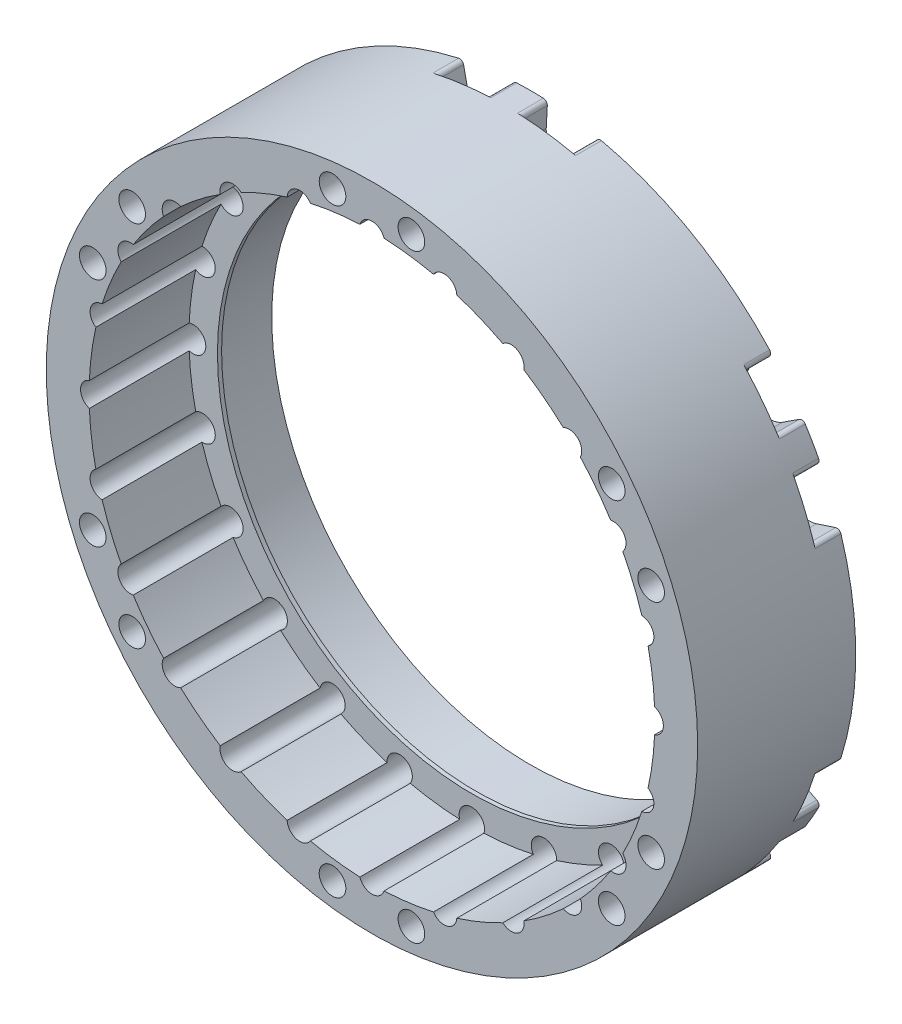
SolidWorks part; units mm, degrees
material "ABS"
ref_plane "Front Plane" through (0, 0, 0) normal (0, 0, 1) x (1, 0, 0)
ref_plane "Top Plane" through (0, 0, 0) normal (0, 1, 0) x (1, 0, 0)
ref_plane "Right Plane" through (0, 0, 0) normal (1, 0, 0) x (0, 0, -1)
sketch "CYC Master Sketch" plane through (0, 0, 0) normal (0, 0, 1) x (1, 0, 0)
  circle A0 centre (0, 0) radius 39.15
  circle A2 centre (0, 0) radius 33.5 construction
  circle A3 centre (-33.5, 0) radius 1.525
  circle A4 centre (-32.3585, 8.6704) radius 1.525
  circle A5 centre (-29.0119, 16.75) radius 1.525
  circle A6 centre (-23.6881, 23.6881) radius 1.525
  circle A7 centre (-16.75, 29.0119) radius 1.525
  circle A8 centre (-8.6704, 32.3585) radius 1.525
  circle A9 centre (0, 33.5) radius 1.525
  circle A10 centre (8.6704, 32.3585) radius 1.525
  circle A11 centre (16.75, 29.0119) radius 1.525
  circle A12 centre (23.6881, 23.6881) radius 1.525
  circle A13 centre (29.0119, 16.75) radius 1.525
  circle A14 centre (32.3585, 8.6704) radius 1.525
  circle A15 centre (33.5, 0) radius 1.525
  circle A16 centre (32.3585, -8.6704) radius 1.525
  circle A17 centre (29.0119, -16.75) radius 1.525
  circle A18 centre (23.6881, -23.6881) radius 1.525
  circle A19 centre (16.75, -29.0119) radius 1.525
  circle A20 centre (8.6704, -32.3585) radius 1.525
  circle A21 centre (0, -33.5) radius 1.525
  circle A22 centre (-8.6704, -32.3585) radius 1.525
  circle A23 centre (0, 0) radius 34
  circle A24 centre (-16.75, -29.0119) radius 1.525
  circle A25 centre (-23.6881, -23.6881) radius 1.525
  circle A26 centre (-29.0119, -16.75) radius 1.525
  circle A27 centre (-32.3585, -8.6704) radius 1.525
  circle A28 centre (0, 0) radius 31.05 construction
  circle A29 centre (0, 0) radius 24.975 construction
  circle A30 centre (0, 0) radius 36.325 construction
  circle A31 centre (4.7414, -36.0142) radius 1.6
  circle A32 centre (-4.7414, -36.0142) radius 1.6
  circle A33 centre (-28.8186, -22.1133) radius 1.6
  circle A34 centre (-33.5599, -13.901) radius 1.6
  circle A35 centre (-33.5599, 13.901) radius 1.6
  circle A36 centre (-28.8186, 22.1133) radius 1.6
  circle A37 centre (-4.7414, 36.0142) radius 1.6
  circle A38 centre (4.7414, 36.0142) radius 1.6
  circle A39 centre (28.8186, 22.1133) radius 1.6
  circle A40 centre (33.5599, 13.901) radius 1.6
  circle A41 centre (33.5599, -13.901) radius 1.6
  circle A42 centre (28.8186, -22.1133) radius 1.6
  point P47 (0, 0)
  point P72 (0, 0)
extrude "Gearbox Wall" add sketch "CYC Master Sketch" along normal blind 19 contours A0 A23 A13 A14 A15 A16 A17 A18 A19 A20 A21 A22 A3 A4 A5 A6 A7 A8 A9 A10 A11 A12 region at (-38.0427, 0, 0)
extrude "Gearbox Bottom" add sketch "CYC Master Sketch<3>" along normal blind 7 contours A21 A23 | A23 A20 | A20 A23 | A23 A19 | A19 A23 | A23 A18 | A18 A23 | A23 A17 | A17 A23 | A23 A16 | A16 A23 | A23 A15 | A15 A23 | A23 A14 | A14 A23 | A23 A13 | A13 A23 | A23 A12 | A12 A23 | A23 A11 | A11 A23 | A23 A10 | A10 A23 | A23 A9 | A9 A23 | A23 A8 | A8 A23 | A23 A7 | A7 A23 | A23 A6 | A6 A23 | A23 A5 | A5 A23 | A23 A4 | A4 A23 | A23 A3 | A3 A23 | A23 A22 | A22 A23 | A13 A23 A12 A11 A10 A9 A8 A7 A6 A5 A4 A3 A22 A21 A20 A19 A18 A17 A16 A15 A14 | A24 | A25 | A26 | A27 | A21 region at (-33.1078, 0, 0) region at (0, 0, 0) region at (-34.4188, 0, 0) region at (-31.9797, 8.5689, 0) region at (-33.246, 8.9082, 0) region at (-28.6722, 16.5539, 0) region at (-29.8076, 17.2094, 0) region at (-23.4108, 23.4108, 0) region at (-24.3378, 24.3378, 0) region at (-16.5539, 28.6722, 0) region at (-17.2094, 29.8076, 0) region at (-8.5689, 31.9797, 0) region at (-8.9082, 33.246, 0) region at (-8.9082, -33.246, 0) region at (-8.5689, -31.9797, 0) region at (0, 33.1078, 0) region at (0, 34.4188, 0) region at (0, -33.1078, 0) region at (8.5689, 31.9797, 0) region at (8.9082, 33.246, 0) region at (8.9082, -33.246, 0) region at (8.5689, -31.9797, 0) region at (16.5539, 28.6722, 0) region at (17.2094, 29.8076, 0) region at (17.2094, -29.8076, 0) region at (16.5539, -28.6722, 0) region at (23.4108, 23.4108, 0) region at (24.3378, 24.3378, 0) region at (24.3378, -24.3378, 0) region at (23.4108, -23.4108, 0) region at (28.6722, 16.5539, 0) region at (29.8076, 17.2094, 0) region at (29.8076, -17.2094, 0) region at (28.6722, -16.5539, 0) region at (31.9797, 8.5689, 0) region at (33.246, 8.9082, 0) region at (33.246, -8.9082, 0) region at (31.9797, -8.5689, 0) region at (33.1078, 0, 0) region at (34.4188, 0, 0)
sketch "CYC Master Sketch<3>" plane through (0, 0, 0) normal (0, 0, 1) x (1, 0, 0) same geometry as "CYC Master Sketch"
extrude "Pin Cut" cut sketch "CYC Master Sketch<2>" against normal blind 4 from surface contours A23 A7 | A7 A23 | A23 A6 | A6 A23 | A23 A5 | A5 A23 | A23 A4 | A4 A23 | A23 A3 | A3 A23 | A23 A22 | A22 A23 | A23 A21 | A21 A23 | A23 A20 | A20 A23 | A23 A19 | A19 A23 | A23 A18 | A18 A23 | A23 A17 | A17 A23 | A16 A23 | A23 A16 | A15 A23 | A23 A15 | A23 A14 | A14 A23 | A23 A13 | A13 A23 | A23 A12 | A12 A23 | A23 A11 | A11 A23 | A10 A23 | A23 A9 | A9 A23 | A23 A8 | A8 A23 | A23 A10 | A23 A24 | A23 A24 | A23 A25 | A23 A25 | A23 A26 | A23 A26 | A23 A27 | A23 A27 region at (-33.1078, 0, 0) region at (-34.4188, 0, 0) region at (-31.9797, 8.5689, 0) region at (-33.246, 8.9082, 0) region at (-31.9797, -8.5689, 0) region at (-33.246, -8.9082, 0) region at (-28.6722, 16.5539, 0) region at (-29.8076, 17.2094, 0) region at (-28.6722, -16.5539, 0) region at (-29.8076, -17.2094, 0) region at (-23.4108, 23.4108, 0) region at (-24.3378, 24.3378, 0) region at (-23.4108, -23.4108, 0) region at (-24.3378, -24.3378, 0) region at (-16.5539, 28.6722, 0) region at (-17.2094, 29.8076, 0) region at (-16.5539, -28.6722, 0) region at (-17.2094, -29.8076, 0) region at (-8.5689, 31.9797, 0) region at (-8.9082, 33.246, 0) region at (-8.9082, -33.246, 0) region at (-8.5689, -31.9797, 0) region at (0, 33.1078, 0) region at (0, 34.4188, 0) region at (0, -34.4188, 0) region at (0, -33.1078, 0) region at (8.5689, 31.9797, 0) region at (8.9082, 33.246, 0) region at (8.9082, -33.246, 0) region at (8.5689, -31.9797, 0) region at (16.5539, 28.6722, 0) region at (17.2094, 29.8076, 0) region at (17.2094, -29.8076, 0) region at (16.5539, -28.6722, 0) region at (23.4108, 23.4108, 0) region at (24.3378, 24.3378, 0) region at (24.3378, -24.3378, 0) region at (23.4108, -23.4108, 0) region at (28.6722, 16.5539, 0) region at (29.8076, 17.2094, 0) region at (29.8076, -17.2094, 0) region at (28.6722, -16.5539, 0) region at (31.9797, 8.5689, 0) region at (33.246, 8.9082, 0) region at (33.246, -8.9082, 0) region at (31.9797, -8.5689, 0) region at (33.1078, 0, 0) region at (34.4188, 0, 0) starting at face at (0, 0, 7)
sketch "CYC Master Sketch<2>" plane through (0, 0, 0) normal (0, 0, 1) x (1, 0, 0) same geometry as "CYC Master Sketch"
sketch "CYC Master" plane through (0, 0, 7) normal (0, 0, 1) x (1, 0, 0)
  circle A0 centre (0, 0) radius 39.15
  circle A2 centre (0, 0) radius 33.5 construction
  circle A3 centre (-33.5, 0) radius 1.525
  circle A4 centre (-32.3585, 8.6704) radius 1.525
  circle A5 centre (-29.0119, 16.75) radius 1.525
  circle A6 centre (-23.6881, 23.6881) radius 1.525
  circle A7 centre (-16.75, 29.0119) radius 1.525
  circle A8 centre (-8.6704, 32.3585) radius 1.525
  circle A9 centre (0, 33.5) radius 1.525
  circle A10 centre (8.6704, 32.3585) radius 1.525
  circle A11 centre (16.75, 29.0119) radius 1.525
  circle A12 centre (23.6881, 23.6881) radius 1.525
  circle A13 centre (29.0119, 16.75) radius 1.525
  circle A14 centre (32.3585, 8.6704) radius 1.525
  circle A15 centre (33.5, 0) radius 1.525
  circle A16 centre (32.3585, -8.6704) radius 1.525
  circle A17 centre (29.0119, -16.75) radius 1.525
  circle A18 centre (23.6881, -23.6881) radius 1.525
  circle A19 centre (16.75, -29.0119) radius 1.525
  circle A20 centre (8.6704, -32.3585) radius 1.525
  circle A21 centre (0, -33.5) radius 1.525
  circle A22 centre (-8.6704, -32.3585) radius 1.525
  circle A23 centre (0, 0) radius 34
  circle A24 centre (-16.75, -29.0119) radius 1.525
  circle A25 centre (-23.6881, -23.6881) radius 1.525
  circle A26 centre (-29.0119, -16.75) radius 1.525
  circle A27 centre (-32.3585, -8.6704) radius 1.525
  circle A28 centre (0, 0) radius 31.05 construction
  circle A29 centre (0, 0) radius 24.975 construction
  circle A30 centre (0, 0) radius 36.325 construction
  circle A31 centre (4.7414, -36.0142) radius 1.6
  circle A32 centre (-4.7414, -36.0142) radius 1.6
  circle A33 centre (-28.8186, -22.1133) radius 1.6
  circle A34 centre (-33.5599, -13.901) radius 1.6
  circle A35 centre (-33.5599, 13.901) radius 1.6
  circle A36 centre (-28.8186, 22.1133) radius 1.6
  circle A37 centre (-4.7414, 36.0142) radius 1.6
  circle A38 centre (4.7414, 36.0142) radius 1.6
  circle A39 centre (28.8186, 22.1133) radius 1.6
  circle A40 centre (33.5599, 13.901) radius 1.6
  circle A41 centre (33.5599, -13.901) radius 1.6
  circle A42 centre (28.8186, -22.1133) radius 1.6
  point P47 (0, 0)
  point P72 (0, 0)
sketch "Sketch2" plane through (0, 0, 7) normal (0, 0, 1) x (1, 0, 0)
  circle A0 centre (0, 0) radius 31.05
  circle A1 centre (0, 0) radius 31.05 construction
extrude "Housing Bearing Cut" cut sketch "Sketch2" against normal through all
sketch "Sketch3" plane through (0, 0, 7) normal (0, 0, 1) x (1, 0, 0)
  circle A0 centre (0, 0) radius 31.05
  circle A1 centre (0, 0) radius 30.575
  circle A2 centre (0, 0) radius 31.05 construction
  dimension "D1" = 61.15
  dimension "Housing Bearing Outer (Driven)" = 62.1
extrude "Housing Bearing Retainer" add sketch "Sketch3" against normal blind 0.5
sketch "Sketch5" plane through (0, 0, 0) normal (0, 0, -1) x (-1, 0, 0)
  line L0 (0, 0) -> (32.2922, 16.3975) construction
  line L1 (0, 0) -> (34.4288, 11.2392) construction
  line L2 (34.4288, 11.2392) -> (37.2171, 12.1494)
  line L3 (32.2922, 16.3975) -> (34.9074, 17.7255)
  line L4 (0, 0) -> (33.9049, 19.575) construction
  line L5 (26.9479, 24.1967) -> (29.1303, 26.1562)
  line L6 (30.3468, 19.7671) -> (32.8045, 21.368)
  line L7 (34.4288, -11.2392) -> (37.2171, -12.1494)
  line L8 (32.2922, -16.3975) -> (34.9074, -17.7255)
  line L9 (26.9479, -24.1967) -> (29.1303, -26.1562)
  line L10 (30.3468, -19.7671) -> (32.8045, -21.368)
  line L11 (7.481, -35.4359) -> (8.0868, -38.3057)
  line L12 (1.9454, -36.1646) -> (2.103, -39.0935)
  line L13 (-7.481, -35.4359) -> (-8.0868, -38.3057)
  line L14 (-1.9454, -36.1646) -> (-2.103, -39.0935)
  line L15 (-26.9479, -24.1967) -> (-29.1303, -26.1562)
  line L16 (-30.3468, -19.7671) -> (-32.8045, -21.368)
  line L17 (-34.4288, -11.2392) -> (-37.2171, -12.1494)
  line L18 (-32.2922, -16.3975) -> (-34.9074, -17.7255)
  line L19 (-34.4288, 11.2392) -> (-37.2171, 12.1494)
  line L20 (-32.2922, 16.3975) -> (-34.9074, 17.7255)
  line L21 (-26.9479, 24.1967) -> (-29.1303, 26.1562)
  line L22 (-30.3468, 19.7671) -> (-32.8045, 21.368)
  line L23 (-7.481, 35.4359) -> (-8.0868, 38.3057)
  line L24 (-1.9454, 36.1646) -> (-2.103, 39.0935)
  line L25 (7.481, 35.4359) -> (8.0868, 38.3057)
  line L26 (1.9454, 36.1646) -> (2.103, 39.0935)
  arc A0 (32.2922, 16.3975) -> (34.4288, 11.2392) centre (33.5599, 13.901) ccw
  arc A1 (-32.8045, -21.368) -> (-29.1303, -26.1562) centre (0, 0) ccw
  circle A2 centre (0, 0) radius 39.15 construction
  arc A3 (34.9074, 17.7255) -> (37.2171, 12.1494) centre (0, 0) cw
  arc A4 (32.8045, 21.368) -> (29.1303, 26.1562) centre (0, 0) ccw
  arc A5 (30.3468, 19.7671) -> (26.9479, 24.1967) centre (28.8186, 22.1133) cw
  arc A6 (34.9074, -17.7255) -> (37.2171, -12.1494) centre (0, 0) ccw
  arc A7 (32.2922, -16.3975) -> (34.4288, -11.2392) centre (33.5599, -13.901) cw
  arc A8 (32.8045, -21.368) -> (29.1303, -26.1562) centre (0, 0) cw
  arc A9 (30.3468, -19.7671) -> (26.9479, -24.1967) centre (28.8186, -22.1133) ccw
  arc A10 (2.103, -39.0935) -> (8.0868, -38.3057) centre (0, 0) ccw
  arc A11 (1.9454, -36.1646) -> (7.481, -35.4359) centre (4.7414, -36.0142) cw
  arc A12 (-2.103, -39.0935) -> (-8.0868, -38.3057) centre (0, 0) cw
  arc A13 (-1.9454, -36.1646) -> (-7.481, -35.4359) centre (-4.7414, -36.0142) ccw
  arc A14 (-30.3468, -19.7671) -> (-26.9479, -24.1967) centre (-28.8186, -22.1133) cw
  arc A15 (-34.9074, -17.7255) -> (-37.2171, -12.1494) centre (0, 0) cw
  arc A16 (-32.2922, -16.3975) -> (-34.4288, -11.2392) centre (-33.5599, -13.901) ccw
  arc A17 (-34.9074, 17.7255) -> (-37.2171, 12.1494) centre (0, 0) ccw
  arc A18 (-32.2922, 16.3975) -> (-34.4288, 11.2392) centre (-33.5599, 13.901) cw
  arc A19 (-32.8045, 21.368) -> (-29.1303, 26.1562) centre (0, 0) cw
  arc A20 (-30.3468, 19.7671) -> (-26.9479, 24.1967) centre (-28.8186, 22.1133) ccw
  arc A21 (-2.103, 39.0935) -> (-8.0868, 38.3057) centre (0, 0) ccw
  arc A22 (-1.9454, 36.1646) -> (-7.481, 35.4359) centre (-4.7414, 36.0142) cw
  arc A23 (2.103, 39.0935) -> (8.0868, 38.3057) centre (0, 0) cw
  arc A24 (1.9454, 36.1646) -> (7.481, 35.4359) centre (4.7414, 36.0142) ccw
  point P39 (0, 0)
  dimension "D1" = 5.6
  dimension "D3" = 6
  dimension "D2" = 7.5
extrude "M3 Socket Head Cutout" cut sketch "Sketch5" against normal blind 3.1
fillet "Fillet1" radius 0.5 24 edges at (-8.0868, -38.3057, 1.55) (-2.103, -39.0935, 1.55) (2.103, -39.0935, 1.55) (8.0868, -38.3057, 1.55) (-29.1303, -26.1562, 1.55) (-32.8045, -21.368, 1.55) (-37.2171, -12.1494, 1.55) (-34.9074, -17.7255, 1.55) (-29.1303, 26.1562, 1.55) (-32.8045, 21.368, 1.55) (-34.9074, 17.7255, 1.55) (-37.2171, 12.1494, 1.55) (-8.0868, 38.3057, 1.55) (-2.103, 39.0935, 1.55) (8.0868, 38.3057, 1.55) (2.103, 39.0935, 1.55) (29.1303, 26.1562, 1.55) (32.8045, 21.368, 1.55) (34.9074, 17.7255, 1.55) (37.2171, 12.1494, 1.55) (37.2171, -12.1494, 1.55) (34.9074, -17.7255, 1.55) (32.8045, -21.368, 1.55) (29.1303, -26.1562, 1.55)
equation "\"D1@Sketch3\" = \"Housing Bearing Outer (Driven)@Sketch3\" - 1"
